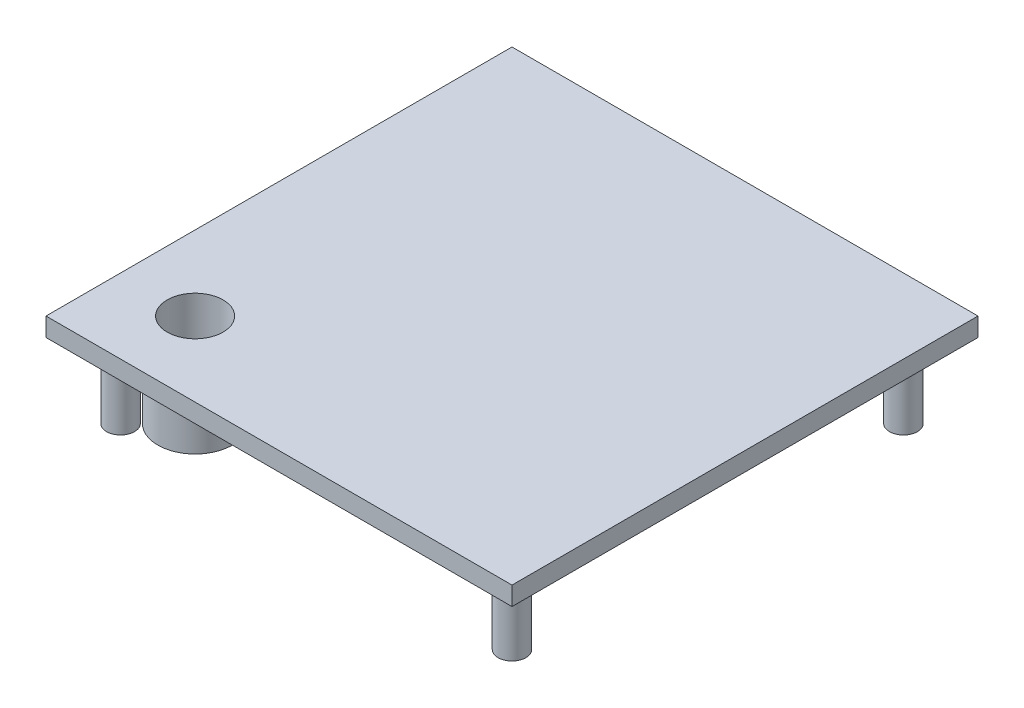
SolidWorks part; units mm, degrees
ref_plane "Front Plane" through (0, 0, 0) normal (0, 0, 1) x (1, 0, 0)
ref_plane "Top Plane" through (0, 0, 0) normal (0, 1, 0) x (1, 0, 0)
ref_plane "Right Plane" through (0, 0, 0) normal (1, 0, 0) x (0, 0, -1)
sketch "Sketch1" plane through (0, 0, 0) normal (0, 1, 0) x (1, 0, 0)
  line L1 (-25, -25) -> (25, -25)
  line L2 (-25, -25) -> (-25, 25)
  line L3 (-25, 25) -> (25, 25)
  line L4 (25, -25) -> (25, 25)
  line L5 (-25, -25) -> (25, 25) construction
  line L6 (-25, 25) -> (25, -25) construction
  point P0 (0, 0)
extrude "Top" add sketch "Sketch1" along normal blind 2
sketch "Sketch2" plane through (0, 0, 0) normal (0, 1, 0) x (1, 0, 0)
  line L15 (-0.522, -3.5) -> (0.4965, -3.5)
  line L21 (-2.0127, -3.5) -> (-2.0127, -5.5)
  line L22 (-0.522, -3.5) -> (-1.1377, -3.5)
  line L26 (-1.1377, -3.5) -> (-2.0127, -3.5)
  line L27 (-2.0127, -5.5) -> (1.9873, -5.5)
  line L29 (1.1123, -3.5) -> (1.9873, -3.5)
  line L32 (0.4965, -3.5) -> (1.1123, -3.5)
  line L33 (1.9873, -3.5) -> (1.9873, -5.5)
  point P21 (-0.0127, -5.5)
extrude "Connecter" add sketch "Sketch2" against normal offset from surface (3 mm away) 3 up to face at (0, 0, 0) offset beyond the face yes
sketch "Sketch3" plane through (0, 0, 0) normal (0, 0, 1) x (1, 0, 0)
  circle A0 centre (-0.0042, -1) radius 0.25
  circle A1 centre (-1.0042, -1) radius 0.25
  circle A2 centre (0.9958, -1) radius 0.25
  point P12 (-4.1588, -1.5245)
extrude "Connecter Cut" cut sketch "Sketch3" along normal blind 10
sketch "Sketch5" plane through (0, 0, 0) normal (0, 0, 1) x (1, 0, 0)
  line L0 (2.9873, 0) -> (1.9873, 0)
  line L1 (-25, 0) -> (25, 0) construction
  line L2 (-2.0127, 0) -> (-3, 0)
  line L3 (-0.0064, -2) -> (-2.0127, -2)
  line L4 (-3, -2.9968) -> (2.9873, -2.9968)
  line L5 (-3, -2.9968) -> (-3, 0)
  line L7 (2.9873, -2.9968) -> (2.9873, 0)
  line L8 (-2.0127, -3) -> (-2.0127, 0) construction
  line L9 (-2.0127, -2) -> (-2.0127, 0)
  line L10 (-0.0064, -2) -> (1.9873, -2)
  line L11 (1.9873, -3) -> (1.9873, 0) construction
  line L12 (1.9873, -2) -> (1.9873, 0)
  point P6 (-0.0064, -1.5)
extrude "Brace" add sketch "Sketch5" along normal blind 5.5 and the other way blind 2
sketch "Sketch6" plane through (0, 0, 0) normal (0, 1, 0) x (1, 0, 0)
  circle A0 centre (-17, -17) radius 3
extrude "LED Cutout" cut sketch "Sketch6" along normal blind 2
sketch "Sketch7" plane through (0, 0, 0) normal (0, -1, 0) x (1, 0, 0)
  circle A1 centre (-17, 17) radius 3
  circle A2 centre (-17, 17) radius 4
extrude "LED Cover" add sketch "Sketch7" along normal blind 7
sketch "Sketch8" plane through (0, 0, 0) normal (0, -1, 0) x (1, 0, 0)
  circle A1 centre (-17, 17) radius 4
  circle A2 centre (-17, 17) radius 2.5
extrude "LED Fastener" add sketch "Sketch8" along normal blind 1 from surface starting at face at (-17, -7, 13)
sketch "Sketch9" plane through (0, 0, 0) normal (0, 1, 0) x (1, 0, 0)
  circle A0 centre (-21, -21) radius 1.5
  circle A1 centre (21, -21) radius 1.5
  circle A2 centre (21, 21) radius 1.5
  circle A3 centre (-21, 21) radius 1.5
extrude "Dowel Joints" add sketch "Sketch9" against normal blind 8
